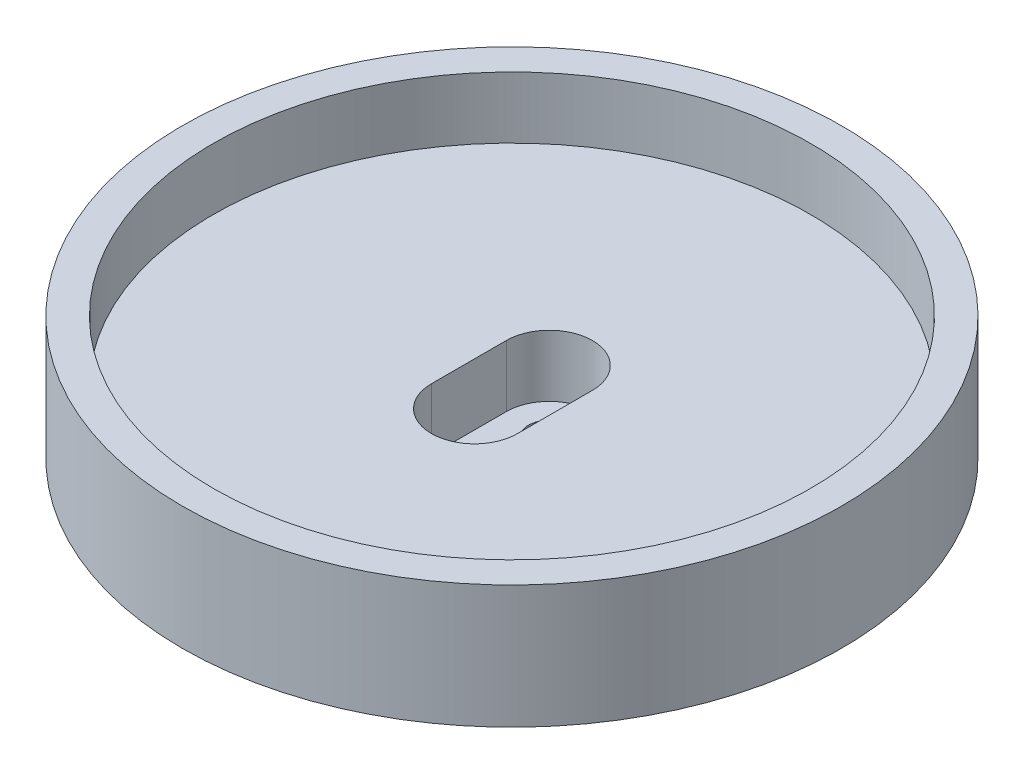
SolidWorks part; units mm, degrees
ref_plane "Front Plane" through (0, 0, 0) normal (0, 0, 1) x (1, 0, 0)
ref_plane "Top Plane" through (0, 0, 0) normal (0, 1, 0) x (1, 0, 0)
ref_plane "Right Plane" through (0, 0, 0) normal (1, 0, 0) x (0, 0, -1)
sketch "Sketch1" plane through (0, 0, 0) normal (0, 1, 0) x (1, 0, 0)
  circle A0 centre (0, 0) radius 26.75
  circle A2 centre (0, 0) radius 25
  dimension "D1" = 50
  dimension "D2" = 53.5
extrude "Boss-Extrude1" add sketch "Sketch1" along normal blind 10 contours A0
sketch "Sketch2" plane through (0, 10, 0) normal (0, 1, 0) x (1, 0, 0)
  circle A0 centre (0, 0) radius 24.25
  circle A1 centre (0, 0) radius 26.75 construction
  dimension "D1" = 2.5
extrude "Cut-Extrude3" cut sketch "Sketch2" against normal blind 5
sketch "Sketch3" plane through (0, 5, 0) normal (0, 1, 0) x (1, 0, 0)
  line L4 (0, 3.0391) -> (0, -3.0391) construction
  line L5 (3.5, 3.0391) -> (3.5, -3.0391)
  line L6 (-3.5, 3.0391) -> (-3.5, -3.0391)
  arc A1 (3.5, 3.0391) -> (-3.5, 3.0391) centre (0, 3.0391) ccw
  arc A2 (-3.5, -3.0391) -> (3.5, -3.0391) centre (0, -3.0391) ccw
  point P1 (0, 0)
  point P4 (0, 0)
  dimension "D1" = 3.5
extrude "Cut-Extrude5" cut sketch "Sketch3" against normal blind 6 contours A2 L5 A1 L6
sketch "Sketch8" plane through (0, 0, 0) normal (0, -1, 0) x (1, 0, 0)
  line L0 (-6, 10) -> (-6, -10)
  line L1 (-6, 10) -> (6, 10)
  line L2 (-6, -10) -> (6, -10)
  line L3 (6, 10) -> (6, -10)
  line L4 (-6, 10) -> (6, -10) construction
  line L5 (-6, -10) -> (6, 10) construction
  point P1 (0, 0)
  dimension "D2" = 20
  dimension "D3" = 6
extrude "Boss-Extrude2" add sketch "Sketch8" along normal blind 4
sketch "Sketch9" plane through (0, 0, 0) normal (0, 1, 0) x (1, 0, 0)
  circle A0 centre (0, 3) radius 1.65
  circle A1 centre (0, -3) radius 1.65
  dimension "D2" = 3.3
  dimension "D5" = 3.3
  dimension "D1" = 3
  dimension "D3" = 6
  dimension "D4" = 3
extrude "Cut-Extrude6" cut sketch "Sketch9" against normal blind 15 contours A0
extrude "Cut-Extrude7" cut sketch "Sketch9<3>" against normal blind 15
sketch "Sketch9<3>" plane through (0, 0, 0) normal (0, 1, 0) x (1, 0, 0) same geometry as "Sketch9"
